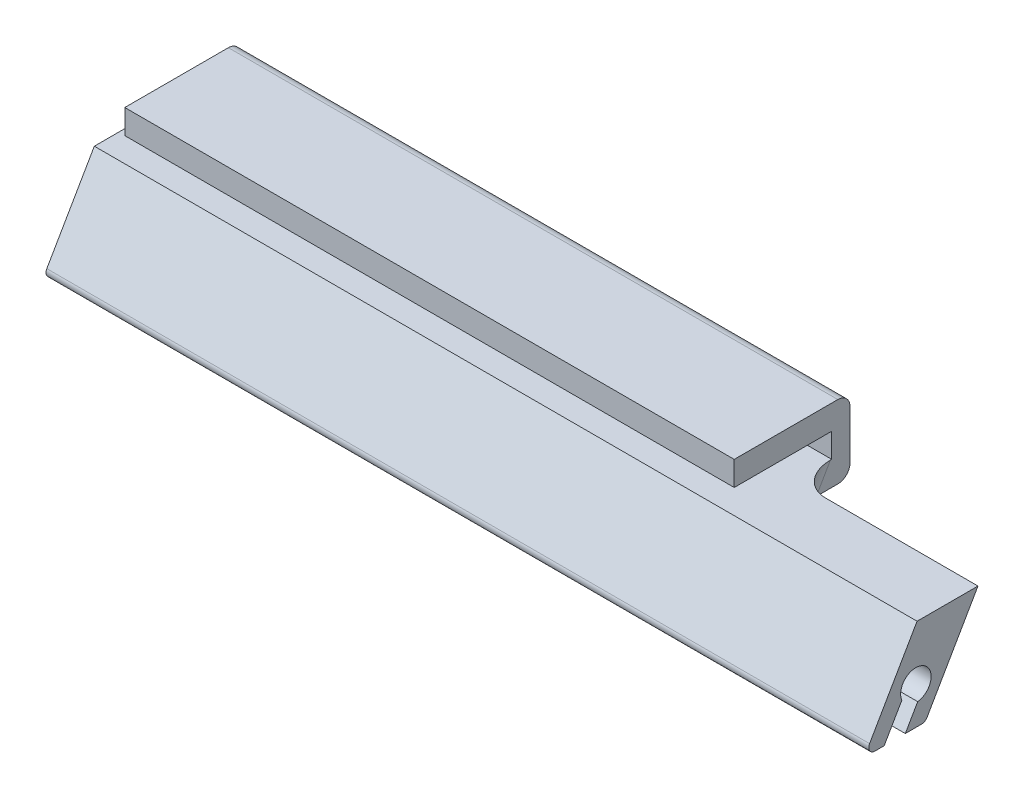
SolidWorks part; units mm, degrees
ref_plane "Front Plane" through (0, 0, 0) normal (0, 0, 1) x (1, 0, 0)
ref_plane "Top Plane" through (0, 0, 0) normal (0, 1, 0) x (1, 0, 0)
ref_plane "Right Plane" through (0, 0, 0) normal (1, 0, 0) x (0, 0, -1)
sketch "Sketch2" plane through (0, 0, 0) normal (1, 0, 0) x (0, 0, -1)
  line L0 (0, 0) -> (8.6603, 15)
  line L1 (8.6603, 15) -> (18.6603, 15)
  line L2 (18.6603, 15) -> (10, 0)
  line L3 (10, 0) -> (0, 0)
  line L4 (0, 0) -> (0, 15) construction
  line L5 (13.6603, 15) -> (5, 0) construction
  line L6 (3.2679, 0) -> (7.1651, 6.75)
  line L7 (7.1651, 6.75) -> (9.7631, 5.25)
  line L8 (9.7631, 5.25) -> (6.7321, 0)
  line L34 (8.6603, 15) -> (27.6603, 15)
  line L35 (8.6603, 15) -> (8.6603, 11)
  line L36 (8.6603, 11) -> (27.6603, 11)
  line L37 (27.6603, 15) -> (27.6603, 11)
  line L38 (27.6603, 15) -> (24.6603, 15)
  line L39 (27.6603, 15) -> (27.6603, 19)
  line L40 (27.6603, 19) -> (24.6603, 19)
  line L41 (24.6603, 15) -> (24.6603, 19)
  line L42 (27.6603, 19) -> (8.6603, 19)
  line L43 (27.6603, 19) -> (27.6603, 23)
  line L44 (27.6603, 23) -> (8.6603, 23)
  line L45 (8.6603, 19) -> (8.6603, 23)
  circle A0 centre (8.4641, 6) radius 2.5
  point P14 (8.4641, 6)
  dimension "D5" = 5
  dimension "D1" = 30
  dimension "D2" = 10
  dimension "D3" = 15
  dimension "D4" = 3
  dimension "D6" = 6
  dimension "D7" = 4
  dimension "D8" = 4
  dimension "D9" = 3
  dimension "D10" = 6
extrude "Boss-Extrude2" add sketch "Sketch2" along normal blind 100 contours L45 L42 L40 L43 L44 | L41 L34 L39 L40 | L37 L34 L2 L36 | L35 L36 L2 L1 | A0 L8 L3 L2 L36 L35 L0 L6
sketch "Sketch3" plane through (100, 0, 0) normal (1, 0, 0) x (0, 0, -1)
  line L0 (0, 0) -> (8.6603, 15)
  line L2 (8.6603, 15) -> (18.6603, 15)
  line L3 (18.6603, 15) -> (10, 0)
  line L4 (10, 0) -> (6.7321, 0)
  line L5 (6.7321, 0) -> (8.7631, 3.5179)
  line L6 (8.7631, 3.5179) -> (6.1651, 5.0179)
  line L7 (6.1651, 5.0179) -> (3.2679, 0)
  line L8 (3.2679, 0) -> (0, 0)
  line L9 (8.6603, 15) -> (24.6603, 15) construction
  line L10 (0, 0) -> (8.6603, 15) construction
  circle A0 centre (8.4641, 6) radius 2.5
  arc A1 (8.7631, 3.5179) -> (6.1651, 5.0179) centre (8.4641, 6) ccw construction
  line M14 (8.6603, 15) -> (0, 0)
  line M15 (0, 0) -> (3.2679, 0)
  line M16 (3.2679, 0) -> (6.1651, 5.0179)
  arc M17 (6.1651, 5.0179) -> (8.7631, 3.5179) centre (8.4641, 6) cw
  line M18 (8.7631, 3.5179) -> (6.7321, 0)
  line M19 (6.7321, 0) -> (10, 0)
  line M20 (10, 0) -> (16.3509, 11)
extrude "Boss-Extrude3" add sketch "Sketch3" along normal blind 30 and the other way blind 105 contours L2 M14 M15 M16 M17 M18 M19 M20
fillet "Fillet5" radius 10 1 edges at (50, 11, -16.3509)
fillet "Fillet6" radius 5 2 edges at (0, 10.5, -16.0622) (100, 10.5, -16.0622)
fillet "Fillet7" radius 2 2 edges at (50, 11, -27.6603) (50, 23, -27.6603)
fillet "Fillet8" radius 1 2 edges at (62.5, 0, -10) (62.5, 0, 0)
